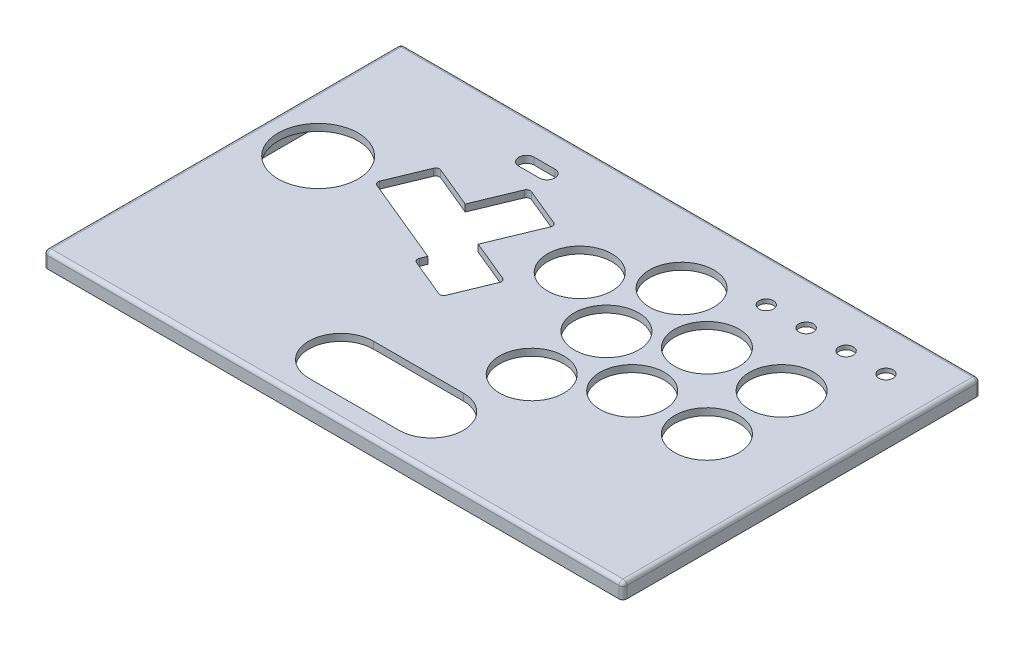
SolidWorks part; units mm, degrees
ref_plane "Front Plane" through (0, 0, 0) normal (0, 0, 1) x (1, 0, 0)
ref_plane "Top Plane" through (0, 0, 0) normal (0, 1, 0) x (1, 0, 0)
ref_plane "Right Plane" through (0, 0, 0) normal (1, 0, 0) x (0, 0, -1)
sketch "Button Cutouts" plane through (0, 0, 0) normal (0, 1, 0) x (1, 0, 0)
  line L0 (24.5, 61) -> (24.5, 32) construction
  line L1 (298.8548, 529.5585) -> (1494.2739, 529.5585) construction
  line L12 (-36.2591, 48.1292) -> (-29.3708, 64.7591) construction
  line L20 (49.5, 75) -> (49.5, 46) construction
  line L21 (78.5, 75) -> (78.5, 46) construction
  line L22 (17.5, 0) -> (-17.5, 0) construction
  line L28 (-36.2591, 48.1292) -> (-19.6292, 41.2409) construction
  line L29 (17.5, -12.5) -> (-17.5, -12.5)
  line L30 (17.5, 12.5) -> (-17.5, 12.5)
  line L31 (24.6803, 89.9994) -> (49.5, 75) construction
  line L32 (24.6803, 89.9994) -> (24.5, 61) construction
  line L33 (-0.5241, 75.6559) -> (24.6803, 89.9994) construction
  line L34 (-0.5241, 75.6559) -> (24.5, 61) construction
  line L48 (-29.3708, 64.7591) -> (-12.7409, 57.8708) construction
  line L49 (-19.6292, 41.2409) -> (-12.7409, 57.8708) construction
  line L50 (-36.2591, 48.1292) -> (-12.7409, 57.8708) construction
  line L51 (-29.3708, 64.7591) -> (-19.6292, 41.2409) construction
  line L52 (-35.6984, 52.2266) -> (-28.8101, 68.8564) construction
  line L53 (-35.6984, 52.2266) -> (-52.3282, 59.1149) construction
  line L54 (-28.8101, 68.8564) -> (-45.4399, 75.7447) construction
  line L55 (-52.3282, 59.1149) -> (-45.4399, 75.7447) construction
  line L56 (-35.6984, 52.2266) -> (-45.4399, 75.7447) construction
  line L57 (-28.8101, 68.8564) -> (-52.3282, 59.1149) construction
  line L58 (-69.9281, 66.405) -> (-63.0398, 83.0348) construction
  line L59 (-69.9281, 66.405) -> (-53.2983, 59.5167) construction
  line L60 (-63.0398, 83.0348) -> (-46.41, 76.1465) construction
  line L61 (-53.2983, 59.5167) -> (-46.41, 76.1465) construction
  line L62 (-69.9281, 66.405) -> (-46.41, 76.1465) construction
  line L63 (-63.0398, 83.0348) -> (-53.2983, 59.5167) construction
  line L64 (-40.5692, 63.9856) -> (-22.9693, 56.6955) construction
  line L65 (-40.5692, 63.9856) -> (-58.1691, 71.2758) construction
  line L66 (-45.0381, 76.7148) -> (-38.1498, 93.3446) construction
  line L67 (-45.0381, 76.7148) -> (-28.4083, 69.8265) construction
  line L68 (-38.1498, 93.3446) -> (-21.52, 86.4563) construction
  line L69 (-28.4083, 69.8265) -> (-21.52, 86.4563) construction
  line L70 (-45.0381, 76.7148) -> (-21.52, 86.4563) construction
  line L71 (-38.1498, 93.3446) -> (-28.4083, 69.8265) construction
  line L72 (-40.5692, 63.9856) -> (-33.2791, 81.5855) construction
  line L73 (-24.5, 53) -> (-22.9693, 56.6955) construction
  line L74 (-58.1691, 71.2758) -> (-65.4592, 53.6759) construction
  line L75 (-65.4592, 53.6759) -> (-90.4039, 64.0083) construction
  line L76 (-70.5814, 66.1344) -> (-63.3104, 83.6881)
  line L77 (-63.3104, 83.6881) -> (-45.7105, 76.398)
  line L78 (-45.7105, 76.398) -> (-38.4204, 93.9979)
  line L79 (-38.4204, 93.9979) -> (-20.8667, 86.7269)
  line L80 (-20.8667, 86.7269) -> (-29.6876, 65.4315)
  line L81 (-29.6876, 65.4315) -> (-12.0877, 58.1414)
  line L82 (-12.0877, 58.1414) -> (-19.3586, 40.5877)
  line L83 (-19.3586, 40.5877) -> (-36.9123, 47.8586)
  line L84 (-36.9123, 47.8586) -> (-35.3816, 51.5542)
  line L85 (-35.3816, 51.5542) -> (-70.5814, 66.1344)
  line L86 (-66.484, 74.7199) -> (-66.9459, 74.9112) construction
  line L87 (-29.6436, 90.3624) -> (-29.8349, 89.9005) construction
  line L88 (-16.1851, 49.5558) -> (-15.7231, 49.3645) construction
  line L89 (-33.2791, 140.3317) -> (-33.2791, 81.5855) construction
  circle A0 centre (24.5, 32) radius 12.5
  circle A1 centre (24.5, 61) radius 12.5
  circle A2 centre (49.5, 46) radius 12.5
  circle A3 centre (49.5, 75) radius 12.5
  circle A4 centre (78.5, 75) radius 12.5
  circle A5 centre (78.5, 46) radius 12.5
  arc A8 (17.5, -12.5) -> (17.5, 12.5) centre (17.5, 0) ccw
  arc A9 (-17.5, 12.5) -> (-17.5, -12.5) centre (-17.5, 0) ccw
  circle A10 centre (-90.4039, 64.0083) radius 15.5
  circle A11 centre (24.6803, 89.9994) radius 12.5
  circle A12 centre (-0.5241, 75.6559) radius 12.5
  point P1 (-24.5, 53)
  point P5 (-40.5692, 63.9856)
  point P6 (-58.1691, 71.2758)
  point P37 (0, 0)
  point P45 (-33.2791, 81.5855)
  point P54 (-30, 0)
  point P55 (30, 0)
  dimension "D2" = 25
  dimension "D12" = 12.5
  dimension "D18" = 31
  dimension "D25" = 22.5
  dimension "D1" = 29
  dimension "D3" = 25
  dimension "D4" = 29
  dimension "D5" = 14
  dimension "D6" = 18
  dimension "D7" = 19.05
  dimension "D8" = 53
  dimension "D9" = 7
  dimension "D10" = 4
  dimension "D11" = 27
  dimension "D13" = 32
  dimension "D14" = 7
  dimension "D15" = 19.05
  dimension "D16" = 0.5
  dimension "D17" = 60
  dimension "D19" = 0.5
  dimension "D20" = 0.5
  dimension "D21" = 29
  dimension "D22" = 29
  dimension "D23" = 0.5
  dimension "D24" = 0.5
sketch "Sketch2" plane through (0, 0, 0) normal (0, 1, 0) x (1, 0, 0)
  line L0 (-105.9039, 64.0083) -> (-112.4039, 64.0083) construction
  line L1 (-112.4039, 118.1994) -> (112.4039, 118.1994)
  line L2 (-112.4039, 118.1994) -> (-112.4039, -20.5)
  line L3 (-112.4039, -20.5) -> (112.4039, -20.5)
  line L4 (112.4039, 118.1994) -> (112.4039, -20.5)
  line L5 (24.6803, 102.4994) -> (24.6803, 118.1994) construction
  line L6 (0, -12.5) -> (0, -20.5) construction
  line L7 (17.5, -12.5) -> (-17.5, -12.5) construction
  circle A0 centre (-90.4039, 64.0083) radius 15.5 construction
  circle A2 centre (24.6803, 89.9994) radius 12.5 construction
  point P4 (0, -20.5)
  dimension "D2" = 6.5
  dimension "D1" = 8
  dimension "D3" = 15.7
  dimension "D4" = 224.8079
  dimension "D5" = 138.6994
extrude "top plate" add sketch "Sketch2" along normal blind 6
extrude "primary button cutouts" cut sketch "Button Cutouts" along normal up to next
fillet "Fillet1" radius 1.5 7 edges at (-20.8667, 3, -86.7269) (-12.0877, 3, -58.1414) (-19.3586, 3, -40.5877) (-36.9123, 3, -47.8586) (-70.5814, 3, -66.1344) (-63.3104, 3, -83.6881) (-38.4204, 3, -93.9979)
sketch "Sketch4" plane through (0, 0, 0) normal (0, -1, 0) x (1, 0, 0)
  line L0 (112.4039, 20.5) -> (112.4039, -118.1994) construction
  line L1 (-106.4039, 14.5) -> (106.4039, 14.5)
  line L2 (-106.4039, 14.5) -> (-106.4039, -112.1994)
  line L3 (-106.4039, -112.1994) -> (106.4039, -112.1994)
  line L4 (106.4039, 14.5) -> (106.4039, -112.1994)
  line L5 (-112.4039, 20.5) -> (112.4039, 20.5) construction
  line L6 (112.4039, -118.1994) -> (-112.4039, -118.1994) construction
  line L7 (-112.4039, -118.1994) -> (-112.4039, 20.5) construction
  dimension "D1" = 6
  dimension "D2" = 6
  dimension "D3" = 6
  dimension "D4" = 6
extrude "Cut-Extrude2" cut sketch "Sketch4" against normal blind 3.3
fillet "Fillet2" radius 1.5 8 edges at (112.4039, 3, -118.1994) (-112.4039, 3, -118.1994) (-112.4039, 3, 20.5) (112.4039, 3, 20.5) (112.4039, 6, -48.8497) (0, 6, -118.1994) (0, 6, 20.5) (-112.4039, 6, -48.8497)
hole_wizard "Tap Drill for M3x0.5 Tap1" positions "3DSketch1" profile "Sketch6" hole size "M3x0.5" standard "ANSI Metric"
sketch3d "3DSketch1"
  line L0 (-108.4039, 0, 16.5) -> (-108.4039, 0, 20.5) construction
  line L1 (-110.9039, 0, 20.5) -> (110.9039, 0, 20.5) construction
  line L3 (-108.4039, 0, 16.5) -> (-112.4039, 0, 16.5)
  line L4 (-112.4039, 0, -116.6994) -> (-112.4039, 0, 19) construction
  line L6 (108.4039, 0, -114.1994) -> (112.4039, 0, -114.1994)
  line L7 (112.4039, 0, 19) -> (112.4039, 0, -116.6994) construction
  line L9 (108.4039, 0, -114.1994) -> (108.4039, 0, -118.1994)
  line L10 (110.9039, 0, -118.1994) -> (-110.9039, 0, -118.1994) construction
  point P0 (-108.4039, 0, 16.5)
  point P2 (-108.4039, 0, -114.1994)
  point P4 (108.4039, 0, -114.1994)
  point P6 (108.4039, 0, 16.5)
  dimension "D1" = 4
sketch "Sketch6" plane through (-108.4039, 0, 16.5) normal (1, 0, 0) x (0, 0, -1)
  line L0 (0, 0) -> (0, 4.7511)
  line L1 (0, 4.7511) -> (1.25, 4)
  line L2 (1.25, 4) -> (1.25, 0)
  line L5 (1.25, 0) -> (0, 0)
  line L10 (0, 4.7511) -> (-1.25, 4) construction
  line L11 (0, -6.35) -> (0, 107.95) construction
  dimension "Hole Dia." = 2.5
  dimension "Hole Depth" = 4
  dimension "Drill Angle" = 118
sketch "Sketch7" plane through (0, 6, 0) normal (0, 1, 0) x (1, 0, 0)
  circle A0 centre (46.5961, 100.92) radius 2.8
  circle A1 centre (62.0961, 100.92) radius 2.8
  circle A2 centre (77.5961, 100.92) radius 2.8
  circle A3 centre (93.0961, 100.92) radius 2.8
  point P0 (93.0961, 100.92)
  dimension "D1" = 5.6
extrude "extra_buttons" cut sketch "Sketch7" against normal up to next
sketch "Sketch8" plane through (0, 6, 0) normal (0, 1, 0) x (1, 0, 0)
  line L0 (-48.0625, 102.5336) -> (-40.0625, 102.5336) construction
  line L1 (-48.0625, 105.5336) -> (-40.0625, 105.5336)
  line L2 (-48.0625, 99.5336) -> (-40.0625, 99.5336)
  arc A0 (-48.0625, 105.5336) -> (-48.0625, 99.5336) centre (-48.0625, 102.5336) ccw
  arc A1 (-40.0625, 99.5336) -> (-40.0625, 105.5336) centre (-40.0625, 102.5336) ccw
  point P2 (-44.0625, 102.5336)
  dimension "D1" = 8
  dimension "D2" = 6
extrude "led_cutout" cut sketch "Sketch8" against normal up to next
sketch "Sketch9" plane through (0, 3.3, 0) normal (0, -1, 0) x (-1, 0, 0)
  line L0 (-93.0961, 100.92) -> (-46.5961, 100.92) construction
  line L1 (-93.0961, 110.92) -> (-46.5961, 110.92)
  line L2 (-93.0961, 90.92) -> (-46.5961, 90.92)
  arc A0 (-93.0961, 110.92) -> (-93.0961, 90.92) centre (-93.0961, 100.92) ccw
  arc A1 (-46.5961, 90.92) -> (-46.5961, 110.92) centre (-46.5961, 100.92) ccw
  circle A2 centre (-93.0961, 100.92) radius 2.8 construction
  circle A3 centre (-46.5961, 100.92) radius 2.8 construction
  point P2 (-69.8461, 100.92)
  dimension "D1" = 10
extrude "Cut-Extrude3" cut sketch "Sketch9" against normal blind 1.1
sketch "Sketch10" plane through (0, 3.3, 0) normal (0, -1, 0) x (1, 0, 0)
  line L0 (-106.4039, -19.5414) -> (-106.4039, -27.5414)
  line L1 (-106.4039, 14.5) -> (-106.4039, -112.1994) construction
  line L2 (-106.4039, 14.5) -> (-106.4039, -112.1994) construction
  line L3 (-106.4039, -27.5414) -> (-44.9537, -27.5414)
  line L4 (-44.9537, -27.5414) -> (-44.9537, 14.5)
  line L5 (106.4039, 14.5) -> (-106.4039, 14.5) construction
  line L6 (-44.9537, 14.5) -> (-52.9537, 14.5)
  line L7 (-52.9537, 14.5) -> (-52.9537, -19.5414)
  line L8 (-52.9537, -19.5414) -> (-106.4039, -19.5414)
  line L9 (60.1524, 14.5) -> (52.1524, 14.5)
  line L10 (106.4039, 14.5) -> (-106.4039, 14.5) construction
  line L11 (52.1524, 14.5) -> (52.1524, -18.7958)
  line L12 (52.1524, -18.7958) -> (106.4039, -18.7958)
  line L13 (106.4039, -112.1994) -> (106.4039, 14.5) construction
  line L14 (106.4039, -18.7958) -> (106.4039, -10.7958)
  line L15 (106.4039, -10.7958) -> (60.1524, -10.7958)
  line L16 (60.1524, -10.7958) -> (60.1524, 14.5)
  dimension "D1" = 8
  dimension "D2" = 8
  dimension "D3" = 8
  dimension "D4" = 8
extrude "Boss-Extrude1" add sketch "Sketch10" along normal up to surface (3.3 mm away) up to face at (-108.4039, 0, 15.25)
